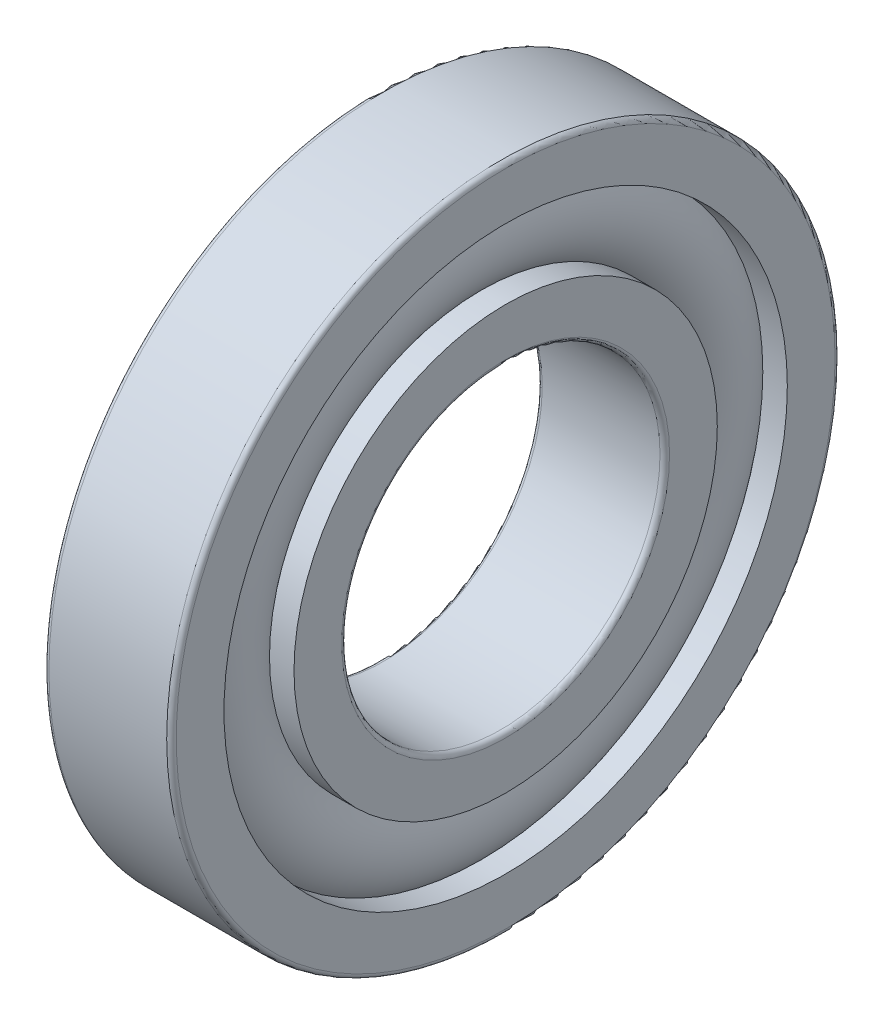
SolidWorks part; units mm, degrees
ref_plane "Plane1" through (0, 0, 0) normal (0, 0, 1) x (1, 0, 0)
ref_plane "Plane2" through (0, 0, 0) normal (0, 1, 0) x (1, 0, 0)
ref_plane "Plane3" through (0, 0, 0) normal (1, 0, 0) x (0, 0, -1)
sketch "Clipboard" plane through (0, 0, 0) normal (0, 0, 1) x (1, 0, 0)
  line L0 (-10, 0) -> (10, 0) construction
  line L1 (0, 0) -> (21.6965, -5.4095)
  line L2 (0, 0) -> (15.4906, 0.5409)
  line L3 (0, 0) -> (22.3471, -0.7804)
  line L4 (0, 0) -> (-22.3573, -0.3902)
  dimension "BallCLRad" = 15.5
sketch "CagSpiSke" plane through (0, 0, 0) normal (0, 0, 1) x (1, 0, 0)
  line L0 (0.33, 14.95) -> (0.33, 16.05)
  line L1 (0.33, 16.05) -> (-0.33, 16.05)
  line L2 (-0.33, 16.05) -> (-0.33, 14.95)
  line L3 (-0.33, 14.95) -> (0.33, 14.95)
  line L4 (-20.6375, 0) -> (20.6375, 0) construction
  line L5 (0, 0) -> (0, 23.7692) construction
  dimension "OD" = 32.1
  dimension "ID" = 29.9
revolve "CageSpine" add sketch "CagSpiSke" angle 360 about L4 reverse direction yes
ref_axis "Axis1" through (-50, 0, 0) along (1, 0, 0)
sketch "CagBalSke" plane through (0, 0, 0) normal (0, 0, 1) x (1, 0, 0)
  line L0 (-3.63, 15.5) -> (3.63, 15.5)
  line L1 (-1.905, 15.5) -> (1.905, 15.5) construction
  line L2 (-10, 0) -> (10, 0) construction
  line L3 (0, 0) -> (0, 24) construction
  arc A0 (3.63, 15.5) -> (-3.63, 15.5) centre (0, 15.5) cw
  dimension "BallCLRad" = 15.5
revolve "CageBall" [suppressed] add sketch "CagBalSke" angle 360 about L1 reverse direction yes
pattern_circular "CageBalls" [suppressed] count 2 every 180 about axis through (-50, 0, 0) along (1, 0, 0)
sketch "CagTrmODSke" plane through (0, 0, 0) normal (0, 0, 1) x (1, 0, 0)
  line L0 (3.631, 16.05) -> (3.631, 19.131)
  line L1 (3.631, 19.131) -> (-3.631, 19.131)
  line L2 (-3.631, 19.131) -> (-3.631, 16.05)
  line L3 (-3.631, 16.05) -> (3.631, 16.05)
  line L4 (-20.6375, 0) -> (20.6375, 0) construction
  line L5 (0, 0) -> (0, 25) construction
  dimension "Width" = 7.262
  dimension "ID" = 32.1
  dimension "OD" = 38.262
revolve "CageTrimOD" [suppressed] cut sketch "CagTrmODSke" angle 360 about L4 reverse direction yes
sketch "CagTrmIDSke" plane through (0, 0, 0) normal (0, 0, 1) x (1, 0, 0)
  line L0 (3.631, 11.871) -> (3.631, 14.95)
  line L1 (3.631, 14.95) -> (-3.631, 14.95)
  line L2 (-3.631, 14.95) -> (-3.631, 11.871)
  line L3 (-3.631, 11.871) -> (3.631, 11.871)
  line L4 (-20.6375, 0) -> (20.6375, 0) construction
  line L5 (0, 0) -> (0, 25) construction
  dimension "Width" = 7.262
  dimension "ID" = 23.742
  dimension "OD" = 29.9
revolve "CageTrimID" [suppressed] cut sketch "CagTrmIDSke" angle 360 about L4 reverse direction yes
sketch "BalSimSke" plane through (0, 0, 0) normal (0, 0, 1) x (1, 0, 0)
  line L0 (-10, 0) -> (10, 0) construction
  line L1 (-10, 15.5) -> (10, 15.5) construction
  line L2 (0, 0) -> (0, 23) construction
  circle A0 centre (0, 15.5) radius 3.3
  dimension "BallCLRad" = 15.5
  dimension "Ball_diameter" = 6.6
revolve "BallsSimplified" add sketch "BalSimSke" angle 360 about L0
sketch "BalDetSke" plane through (0, 0, 0) normal (0, 0, 1) x (1, 0, 0)
  line L0 (-3.3, 15.5) -> (3.3, 15.5)
  line L1 (-1.905, 15.5) -> (1.905, 15.5) construction
  line L2 (0, 0) -> (0, 25) construction
  arc A0 (3.3, 15.5) -> (-3.3, 15.5) centre (0, 15.5) cw
  dimension "BallCLRad" = 15.5
  dimension "Ball_diameter" = 6.6
revolve "BallDetailed" [suppressed] add sketch "BalDetSke" angle 360 about L1 reverse direction yes
sketch "InnRacSke" plane through (0, 0, 0) normal (0, 0, 1) x (1, 0, 0)
  line L0 (-2.426, 13.3) -> (-4, 13.3)
  line L1 (-4, 13.3) -> (-4, 10.3)
  line L2 (-3.7, 10) -> (3.7, 10)
  line L3 (4, 10.3) -> (4, 13.3)
  line L4 (4, 13.3) -> (2.426, 13.3)
  line L5 (-20.6375, 0) -> (20.6375, 0) construction
  line L6 (0, 0) -> (0, 30) construction
  arc A0 (-4, 10.3) -> (-3.7, 10) centre (-3.7, 10.3) ccw
  arc A1 (3.7, 10) -> (4, 10.3) centre (3.7, 10.3) ccw
  arc A2 (2.426, 13.3) -> (-2.426, 13.3) centre (0, 15.5) cw
  dimension "BallCLRad" = 15.5
  dimension "Fillet_radius" = 0.3
  dimension "Ball_diameter" = 6.55
  dimension "ID" = 20
  dimension "OD" = 26.6
  dimension "Width" = 8
revolve "InnerRace" add sketch "InnRacSke" angle 360 about L5 reverse direction yes
sketch "OutRacSke" plane through (0, 0, 0) normal (0, 0, 1) x (1, 0, 0)
  line L0 (-2.426, 17.7) -> (-4, 17.7)
  line L1 (-4, 17.7) -> (-4, 20.7)
  line L2 (-3.7, 21) -> (3.7, 21)
  line L3 (4, 20.7) -> (4, 17.7)
  line L4 (4, 17.7) -> (2.426, 17.7)
  line L5 (-20.6375, 0) -> (20.6375, 0) construction
  line L6 (0, 0) -> (0, 30) construction
  arc A0 (-4, 20.7) -> (-3.7, 21) centre (-3.7, 20.7) cw
  arc A1 (3.7, 21) -> (4, 20.7) centre (3.7, 20.7) cw
  arc A2 (2.426, 17.7) -> (-2.426, 17.7) centre (0, 15.5) ccw
  dimension "BallCLRad" = 15.5
  dimension "Fillet_radius" = 0.3
  dimension "Ball_diameter" = 6.55
  dimension "Width" = 8
revolve "OuterRace" add sketch "OutRacSke" angle 360 about L5 reverse direction yes
pattern_circular "BallsDetailed" [suppressed] count 2 every 180 about axis through (-50, 0, 0) along (1, 0, 0)
equation "\"BallCLRad@Clipboard\" = ( \"OD@OutRacSke\" + \"ID@InnRacSke\" ) / 4"
equation "\"BallCLRad@BalSimSke\" = \"BallCLRad@Clipboard\""
equation "\"BallCLRad@BalDetSke\" = \"BallCLRad@Clipboard\""
equation "\"BallCLRad@InnRacSke\" = \"BallCLRad@Clipboard\""
equation "\"BallCLRad@OutRacSke\" = \"BallCLRad@Clipboard\""
equation "\"Ball_diameter@InnRacSke\" = \"Ball_diameter@BalDetSke\" - 0.05"
equation "\"Ball_diameter@OutRacSke\" = \"Ball_diameter@BalDetSke\" - 0.05"
equation "\"Ball_diameter@BalSimSke\" = \"Ball_diameter@BalDetSke\""
equation "\"Width@OutRacSke\" = \"Width@InnRacSke\""
equation "\"Fillet_radius@OutRacSke\" = \"Fillet_radius@InnRacSke\""
equation "\"Max_count@Clipboard\" = int( 3.14159265 / atn(( \"Ball_diameter@BalDetSke\" / 2) / sqr( \"BallCLRad@Clipboard\"  *  \"BallCLRad@Clipboard\" - ( \"Ball_diameter@BalDetSke\" / 2) *  ( \"Ball_diameter@BalDetSke\" / 2))))"
equation "\"Max_count@Clipboard\" = ((sgn( \"Max_count@Clipboard\" - \"Count@Clipboard\" )-1)*( \"Max_count@Clipboard\" - \"Count@Clipboard\" ))/-2+ \"Count@Clipboard\""
equation "\"Count@BallsDetailed\" = int( \"Show_count@Clipboard\" ) "
equation "\"Count@BallsDetailed\" = ((sgn( \"Count@BallsDetailed\" - \"Max_count@Clipboard\" )-1)*( \"Count@BallsDetailed\" - \"Max_count@Clipboard\" ))/-2+ \"Max_count@Clipboard\""
equation "\"Count@BallsDetailed\" = ((sgn( \"Count@BallsDetailed\" - \"Min_count@Clipboard\" )+1)*( \"Count@BallsDetailed\" - \"Min_count@Clipboard\"))/2 +\"Min_count@Clipboard\""
equation "\"Angle@BallsDetailed\" = 360.0 / \"Max_count@Clipboard\""
equation "\"BallCLRad@CagBalSke\" = \"BallCLRad@Clipboard\""
equation "\"Count@CageBalls\" = \"Count@BallsDetailed\""
equation "\"Angle@CageBalls\" = \"Angle@BallsDetailed\""
equation "\"Angle@CageSpine\" =  \"Angle@CageBalls\" * ( \"Count@CageBalls\" -1 + int( \"Count@CageBalls\" / \"Max_count@Clipboard\" ) )  + 0.001 -  int( \"Count@CageBalls\" / \"Max_count@Clipboard\" ) * 0.001"
equation "\"Angle@CageSpine\" =  \"Angle@CageSpine\" * int( \"Min_count@Clipboard\" / 2) + int(1 / \"Min_count@Clipboard\")  * 0.001"
equation "\"CageWallOD@CagBalSke\" =  \"Ball_diameter@BalDetSke\" * 1.1"
equation "\"Thickness@CagSpiSke\" =  \"Ball_diameter@BalDetSke\" * 0.1"
equation "\"OD@CagTrmODSke\" = \"BallCLRad@Clipboard\" * 2 + \"CageWallOD@CagBalSke\" + 0.002"
equation "\"ID@CagTrmODSke\" = \"BallCLRad@Clipboard\" * 2 + \"Ball_diameter@BalDetSke\" / 6"
equation "\"OD@CagTrmIDSke\" = \"BallCLRad@Clipboard\" * 2 - \"Ball_diameter@BalDetSke\" / 6"
equation "\"ID@CagTrmIDSke\" = \"BallCLRad@Clipboard\" * 2 - \"CageWallOD@CagBalSke\" + 0.002"
equation "\"OD@CagSpiSke\" = \"ID@CagTrmODSke\""
equation "\"ID@CagSpiSke\" = \"OD@CagTrmIDSke\""
equation "\"Width@CagTrmODSke\" = \"CageWallOD@CagBalSke\" + 0.002"
equation "\"Width@CagTrmIDSke\" = \"CageWallOD@CagBalSke\" + 0.002"
